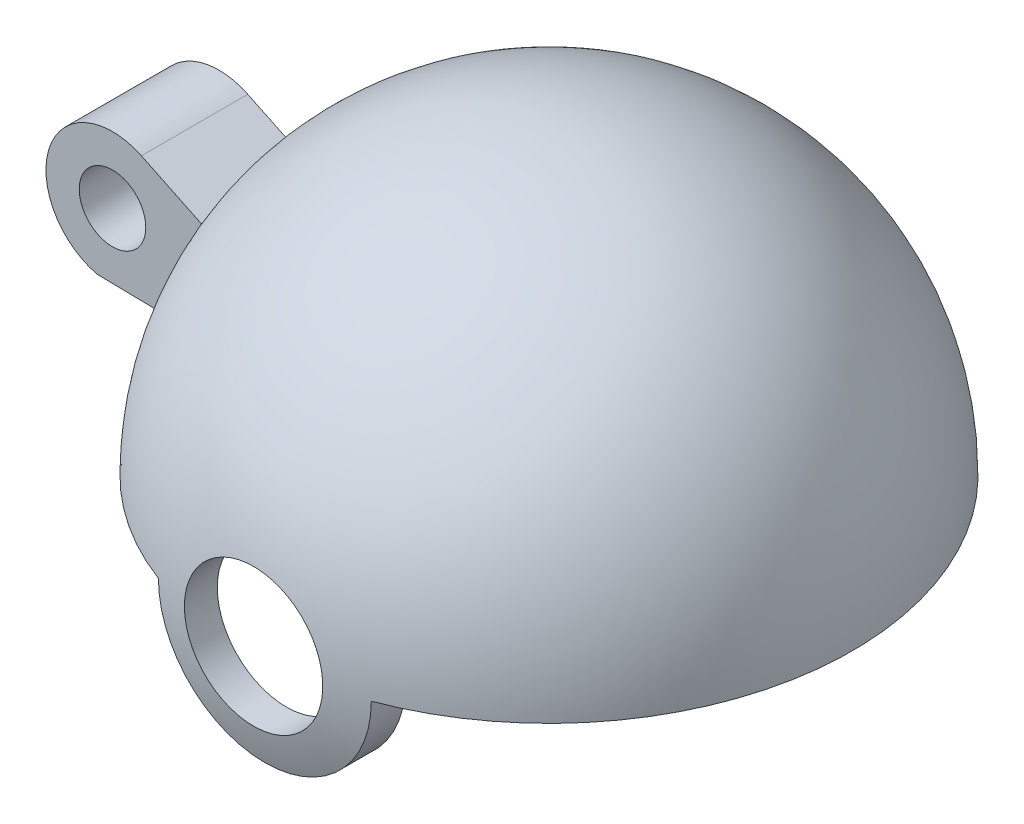
SolidWorks part; units mm, degrees
ref_plane "Front Plane" through (0, 0, 0) normal (0, 0, 1) x (1, 0, 0)
ref_plane "Top Plane" through (0, 0, 0) normal (0, 1, 0) x (1, 0, 0)
ref_plane "Right Plane" through (0, 0, 0) normal (1, 0, 0) x (0, 0, -1)
sketch "Sketch1" plane through (0, 0, 0) normal (0, 0, 1) x (1, 0, 0)
  line L1 (0, 0) -> (0, 14.478) construction
  line L2 (0, 14.478) -> (0, -14.478)
  arc A1 (0, 14.478) -> (0, -14.478) centre (0, 0) ccw
  arc A2 (0, 12.954) -> (0, -12.954) centre (0, 0) ccw
  dimension "D1" = 12.954
  dimension "D2" = 14.478
revolve "Revolve1" add sketch "Sketch1" angle 360 about L1 region at (-0.3237, 13.716, 0)
sketch "Sketch5" plane through (0, 0, 0) normal (0, 0, 1) x (1, 0, 0)
  line L0 (-13.7551, 4.5177) -> (-13.5099, 4.5177)
  line L1 (-14.478, 0) -> (-14.2328, 0)
  line L2 (-14.478, 0) -> (-19.029, 0.0877)
  line L3 (-14.478, 0) -> (-13.7551, 4.5177)
  line L4 (-16.9116, 6.0361) -> (-13.7551, 4.5177)
  line L5 (-13.5099, 4.5177) -> (-14.2328, 0)
  circle A3 centre (-18.288, 3.175) radius 3.175
  circle A4 centre (-18.288, 3.175) radius 1.5875
  circle A5 centre (0, 0) radius 14.478 construction
  dimension "D1" = 6.35
  dimension "D2" = 3.175
  dimension "D3" = 3.175
  dimension "D4" = 3.81
extrude "Boss-Extrude2" add sketch "Sketch5" against normal blind 5.08 from offset 2.54 contours A3 A4 | A3 L3 | L5 L0 L3 region at (-13.9939, 2.2588, 0) region at (-14.9919, 2.3943, 0) region at (-15.6757, 4.8172, 0)
sketch "Sketch7" plane through (0, 0, 0) normal (0, 0, 1) x (1, 0, 0)
  circle A0 centre (0, 0) radius 3.302
  dimension "D1" = 6.604
extrude "Cut-Extrude2" cut sketch "Sketch7" against normal through all both and the other way through all
sketch "Sketch8" plane through (0, 0, 0) normal (0, 0, 1) x (1, 0, 0)
  line L0 (-14.478, 0) -> (-5.08, 0)
  line L1 (14.478, 0) -> (5.08, 0)
  arc A0 (-14.478, 0) -> (-13.7551, 4.5177) centre (0, 0) ccw construction
  arc A1 (5.08, 0) -> (-5.08, 0) centre (0, 0) cw
  dimension "D1" = 5.08
extrude "Cut-Extrude3" cut sketch "Sketch8" against normal through all both and the other way through all
